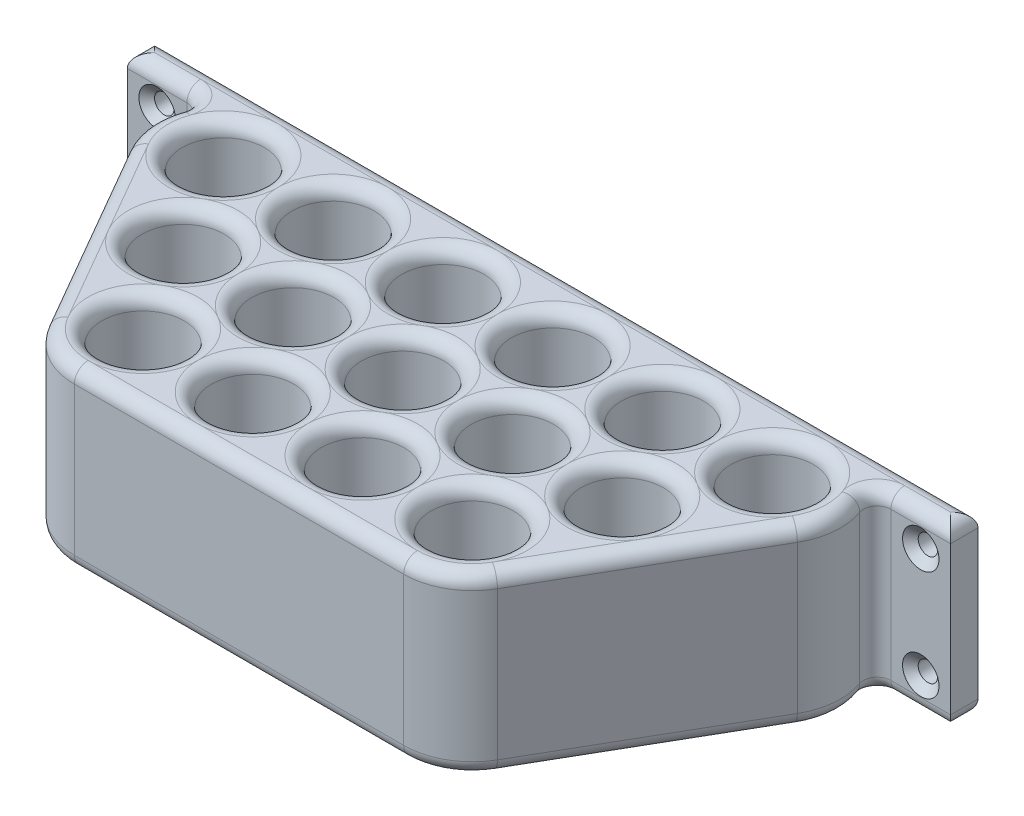
SolidWorks part; units mm, degrees
ref_plane "Front Plane" through (0, 0, 0) normal (0, 0, 1) x (1, 0, 0)
ref_plane "Top Plane" through (0, 0, 0) normal (0, 1, 0) x (1, 0, 0)
ref_plane "Right Plane" through (0, 0, 0) normal (1, 0, 0) x (0, 0, -1)
sketch "Sketch1" plane through (0, 0, 0) normal (0, 1, 0) x (1, 0, 0)
  line L0 (-25.4, 43.9941) -> (0, 43.9941) construction
  line L1 (0, 43.9941) -> (25.4, 43.9941) construction
  line L2 (25.4, 43.9941) -> (12.7, 21.997) construction
  line L3 (12.7, 21.997) -> (0, 0) construction
  line L4 (0, 0) -> (-12.7, 21.997) construction
  line L5 (-12.7, 21.997) -> (12.7, 21.997) construction
  line L6 (12.7, 21.997) -> (0, 43.9941) construction
  line L7 (0, 43.9941) -> (-12.7, 21.997) construction
  line L8 (-12.7, 21.997) -> (-25.4, 43.9941) construction
  line L9 (25.4, 43.9941) -> (50.8, 43.9941) construction
  line L10 (-25.4, 59.8691) -> (101.6, 59.8691)
  line L11 (115.3482, 36.0566) -> (89.9482, -7.9375)
  line L12 (0, -15.875) -> (76.2, -15.875)
  line L13 (-39.1482, 36.0566) -> (-13.7482, -7.9375)
  line L14 (-39.1482, 36.0566) -> (-33.6489, 39.2316) construction
  line L15 (-25.4, 59.8691) -> (-25.4, 53.5191) construction
  line L16 (-15.875, 43.9941) -> (-9.525, 43.9941) construction
  circle A0 centre (0, 0) radius 9.525
  circle A1 centre (-12.7, 21.997) radius 9.525
  circle A2 centre (12.7, 21.997) radius 9.525
  circle A3 centre (-25.4, 43.9941) radius 9.525
  circle A4 centre (0, 43.9941) radius 9.525
  circle A5 centre (25.4, 43.9941) radius 9.525
  circle A6 centre (50.8, 43.9941) radius 9.525
  circle A7 centre (38.1, 21.997) radius 9.525
  circle A8 centre (25.4, 0) radius 9.525
  circle A9 centre (76.2, 43.9941) radius 9.525
  circle A10 centre (63.5, 21.997) radius 9.525
  circle A11 centre (50.8, 0) radius 9.525
  circle A12 centre (101.6, 43.9941) radius 9.525
  circle A13 centre (88.9, 21.997) radius 9.525
  circle A14 centre (76.2, 0) radius 9.525
  arc A15 (-39.1482, 36.0566) -> (-25.4, 59.8691) centre (-25.4, 43.9941) cw
  arc A16 (101.6, 59.8691) -> (115.3482, 36.0566) centre (101.6, 43.9941) cw
  arc A17 (89.9482, -7.9375) -> (76.2, -15.875) centre (76.2, 0) cw
  arc A18 (-13.7482, -7.9375) -> (0, -15.875) centre (0, 0) ccw
  point P39 (-15.875, 43.9941)
  point P41 (-9.525, 43.9941)
  dimension "D1" = 19.05
  dimension "D2" = 25.4
  dimension "D3" = 4
extrude "Boss-Extrude1" add sketch "Sketch1" along normal mid plane 38.1
sketch "Sketch2" plane through (0, -19.05, 0) normal (0, -1, 0) x (1, 0, 0)
  line L4 (-25.4, -59.8691) -> (101.6, -59.8691)
  line L5 (115.3482, -36.0566) -> (89.9482, 7.9375)
  line L6 (76.2, 15.875) -> (0, 15.875)
  line L7 (-13.7482, 7.9375) -> (-39.1482, -36.0566)
  line L8 (-25.4, -59.8691) -> (101.6, -59.8691)
  line L9 (115.3482, -36.0566) -> (89.9482, 7.9375)
  line L10 (76.2, 15.875) -> (0, 15.875)
  line L11 (-13.7482, 7.9375) -> (-39.1482, -36.0566)
  arc A4 (-39.1482, -36.0566) -> (-25.4, -59.8691) centre (-25.4, -43.9941) ccw
  arc A5 (101.6, -59.8691) -> (115.3482, -36.0566) centre (101.6, -43.9941) ccw
  arc A6 (89.9482, 7.9375) -> (76.2, 15.875) centre (76.2, 0) ccw
  arc A7 (0, 15.875) -> (-13.7482, 7.9375) centre (0, 0) ccw
  arc A8 (-39.1482, -36.0566) -> (-25.4, -59.8691) centre (-25.4, -43.9941) ccw
  arc A9 (101.6, -59.8691) -> (115.3482, -36.0566) centre (101.6, -43.9941) ccw
  arc A10 (89.9482, 7.9375) -> (76.2, 15.875) centre (76.2, 0) ccw
  arc A11 (0, 15.875) -> (-13.7482, 7.9375) centre (0, 0) ccw
  dimension "D1" = 0
extrude "Boss-Extrude2" add sketch "Sketch2" along normal blind 2.54
sketch "Sketch3" plane through (0, 0, -59.8691) normal (0, 0, -1) x (-1, 0, 0)
  line L0 (25.4, -21.59) -> (-101.6, -21.59) construction
  line L1 (-133.35, -21.59) -> (57.15, -21.59)
  line L2 (-133.35, -21.59) -> (-133.35, 19.05)
  line L3 (-133.35, 19.05) -> (57.15, 19.05)
  line L4 (57.15, -21.59) -> (57.15, 19.05)
  line L5 (-133.35, -21.59) -> (57.15, 19.05) construction
  line L6 (-133.35, 19.05) -> (57.15, -21.59) construction
  line L7 (-101.6, 19.05) -> (25.4, 19.05) construction
  line L8 (41.275, -21.59) -> (41.275, 19.05) construction
  point P0 (-38.1, -1.27)
  point P5 (-38.1, -5.1435)
  point P8 (-38.1, -21.59)
  point P11 (66.9603, -21.59)
  dimension "D1" = 15.875
extrude "Boss-Extrude3" add sketch "Sketch3" against normal blind 6.35
fillet "Fillet1" radius 3.175 56 edges at (102.6482, 19.05, -14.0595) (84.1375, 19.05, 13.7482) (38.1, 19.05, 15.875) (-7.9375, 19.05, 13.7482) (-26.4482, 19.05, -14.0595) (-41.2465, 19.05, -44.9452) (-47.625, 19.05, -53.5191) (-57.15, 19.05, -56.6941) (38.1, 19.05, -59.8691) (133.35, 19.05, -56.6941) (123.825, 19.05, -53.5191) (117.4465, 19.05, -44.9452) (-26.4482, -21.59, -14.0595) (-7.9375, -21.59, 13.7482) (38.1, -21.59, 15.875) (84.1375, -21.59, 13.7482) (102.6482, -21.59, -14.0595) (117.4465, -21.59, -44.9452) (123.825, -21.59, -53.5191) (133.35, -21.59, -56.6941) (38.1, -21.59, -59.8691) (-57.15, -21.59, -56.6941) (-47.625, -21.59, -53.5191) (-41.2465, -21.59, -44.9452) (101.6, 19.05, -34.4691) (101.6, -19.05, -34.4691) (76.2, 19.05, -34.4691) (76.2, -19.05, -34.4691) (50.8, 19.05, -34.4691) (50.8, -19.05, -34.4691) (-25.4, 19.05, -34.4691) (-25.4, -19.05, -34.4691) (0, 19.05, -34.4691) (0, -19.05, -34.4691) (25.4, 19.05, -34.4691) (25.4, -19.05, -34.4691) (38.1, -19.05, -12.472) (38.1, 19.05, -12.472) (12.7, -19.05, -12.472) (12.7, 19.05, -12.472) (-12.7, -19.05, -12.472) (-12.7, 19.05, -12.472) (0, -19.05, 9.525) (0, 19.05, 9.525) (25.4, -19.05, 9.525) (25.4, 19.05, 9.525) (50.8, -19.05, 9.525) (50.8, 19.05, 9.525) (76.2, -19.05, 9.525) (76.2, 19.05, 9.525) (63.5, -19.05, -12.472) (63.5, 19.05, -12.472) (88.9, -19.05, -12.472) (88.9, 19.05, -12.472) (-38.1, -1.27, -53.5191) (114.3, -1.27, -53.5191)
hole_wizard "CSK for #8 Flat Head Machine Screw (100)1" positions "3DSketch1" profile "Sketch4" countersink size "#8" standard "ANSI Inch" end condition through all
sketch3d "3DSketch1"
  line L0 (-57.15, 15.875, -53.5191) -> (-43.3605, -18.415, -53.5191) construction
  line L2 (-50.2553, 11.43, -53.5191) -> (-50.2553, -13.97, -53.5191) construction
  point P0 (-50.2553, 11.43, -53.5191)
  point P2 (-50.2553, -13.97, -53.5191)
  point P18 (-50.2553, -1.27, -53.5191)
  point P19 (-50.2553, -1.27, -53.5191)
  dimension "D1" = 25.4
sketch "Sketch4" plane through (-50.2553, 11.43, -53.5191) normal (1, 0, 0) x (0, -1, 0)
  line L0 (0, 0) -> (0, 6.35)
  line L1 (0, 6.35) -> (2.2479, 6.35)
  line L2 (2.2479, 6.35) -> (2.2479, 1.6518)
  line L3 (2.2479, 1.6518) -> (4.2164, 0)
  line L5 (4.2164, 0) -> (0, 0)
  line L6 (-2.2479, 1.6518) -> (-4.2164, 0) construction
  line L11 (0, -6.35) -> (0, 107.95) construction
  dimension "Thru Hole Dia." = 4.4958
  dimension "Thru Hole Depth" = 6.35
  dimension "Near C'Sink Dia." = 8.4328
  dimension "Near C'Sink Angle" = 100
ref_plane "Plane1" through (38.1, 0, 0) normal (-1, 0, 0) x (0, 0, 1)
mirror "Mirror1" about plane through (38.1, 0, 0) normal (-1, 0, 0) of "CSK for #8 Flat Head Machine Screw (100)1"
